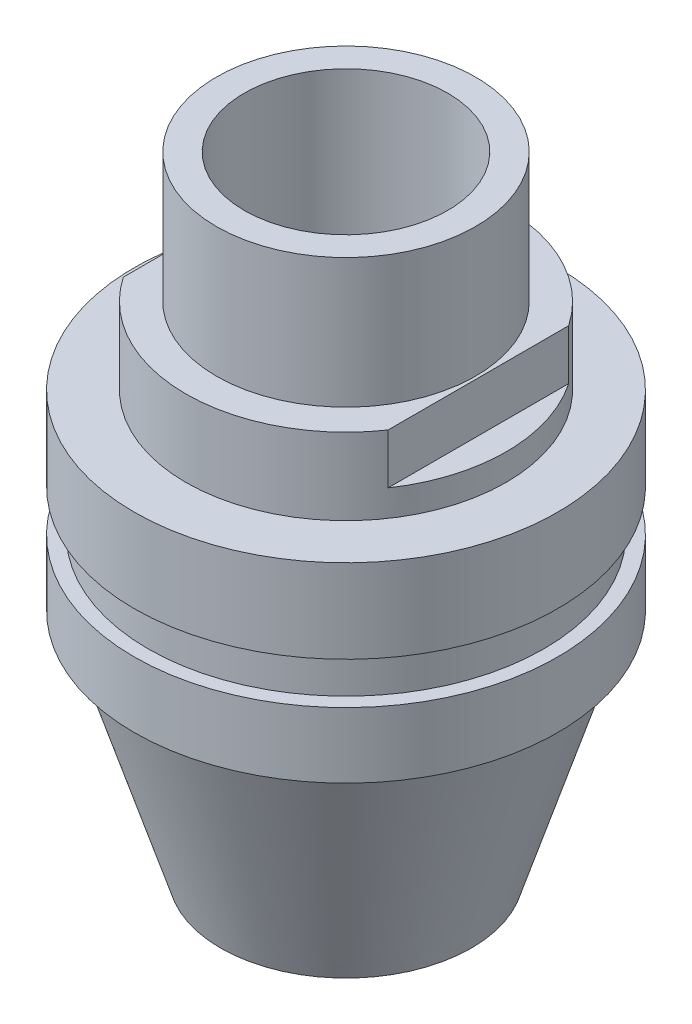
SolidWorks part; units mm, degrees
ref_plane "Front Plane" through (0, 0, 0) normal (0, 0, 1) x (1, 0, 0)
ref_plane "Top Plane" through (0, 0, 0) normal (0, 1, 0) x (1, 0, 0)
ref_plane "Right Plane" through (0, 0, 0) normal (1, 0, 0) x (0, 0, -1)
sketch "Sketch1" plane through (0, 0, 0) normal (0, 0, 1) x (1, 0, 0)
  line L0 (0, 0) -> (0, -22.5) construction
  line L1 (0, 0) -> (0, -22.5)
  line L2 (0, 0) -> (4.65, 0)
  line L3 (4.65, 0) -> (4.65, -4.65)
  line L4 (4.65, -4.65) -> (5.75, -4.65)
  line L5 (5.75, -4.65) -> (5.75, -7.4)
  line L6 (5.75, -7.4) -> (7.6, -7.4)
  line L7 (7.6, -7.4) -> (7.6, -10.4)
  line L8 (7.6, -10.4) -> (7.1, -10.4)
  line L9 (7.1, -10.4) -> (7.1, -11.9)
  line L10 (7.1, -11.9) -> (7.6, -11.9)
  line L11 (7.6, -11.9) -> (7.6, -14.25)
  line L12 (7.6, -14.25) -> (7.1, -14.25)
  line L13 (7.1, -14.25) -> (4.5, -22.5)
  line L14 (4.5, -22.5) -> (0, -22.5)
  dimension "D1" = 22.5
  dimension "D2" = 4.65
  dimension "D3" = 4.65
  dimension "D4" = 5.75
  dimension "D5" = 2.75
  dimension "D6" = 7.6
  dimension "D7" = 3
  dimension "D8" = 1.5
  dimension "D9" = 0.5
  dimension "D10" = 8.25
  dimension "D11" = 4.5
  dimension "D12" = 0.5
revolve "Revolve1" add sketch "Sketch1" angle 360 about L0
sketch "Sketch2" plane through (0, -4.65, 0) normal (0, 1, 0) x (1, 0, 0)
  line L0 (4.75, 3.2404) -> (4.75, -3.2404)
  line L1 (-4.75, 3.2404) -> (-4.75, -3.2404)
  circle A0 centre (0, 0) radius 5.75 construction
  circle A1 centre (0, 0) radius 5.75
  circle A2 centre (0, 0) radius 5.75 construction
  circle M2 centre (0, 0) radius 5.75
  dimension "D1" = 9.5
extrude "Cut-Extrude1" cut sketch "Sketch2" against normal blind 1.8 contours L1 M2 | L0 M2 region at (5.1531, -4.65, 0) region at (-5.1531, -4.65, 0)
shell "Shell1" thickness 1 removed face at (0, 0, 4.65)
sketch "Sketch3" plane through (0, -21.5, 0) normal (0, 1, 0) x (1, 0, 0)
  circle A0 centre (0, 0) radius 3.7667
  circle A1 centre (0, 0) radius 3.7667 construction
extrude "Cut-Extrude2" cut sketch "Sketch3" against normal blind 6.8
